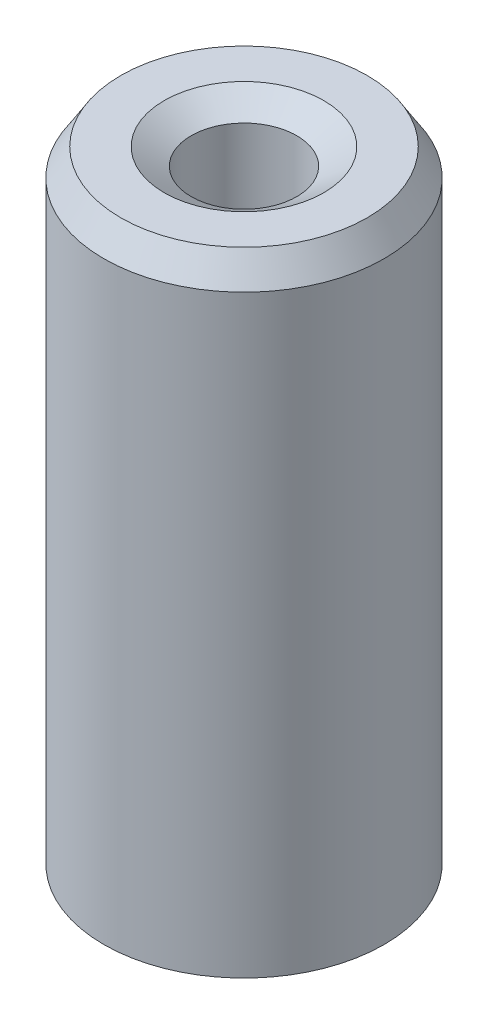
SolidWorks part; units mm, degrees
ref_plane "Front Plane" through (0, 0, 0) normal (0, 0, 1) x (1, 0, 0)
ref_plane "Top Plane" through (0, 0, 0) normal (0, 1, 0) x (1, 0, 0)
ref_plane "Right Plane" through (0, 0, 0) normal (1, 0, 0) x (0, 0, -1)
sketch "Sketch1" plane through (0, 0, 0) normal (0, 1, 0) x (1, 0, 0)
  circle A0 centre (0, 0) radius 12.5
  dimension "SLEEVE_OD" = 25
extrude "Boss-Extrude1" add sketch "Sketch1" along normal blind 56.8938
sketch "Sketch2" plane through (0, 0, 0) normal (0, 1, 0) x (1, 0, 0)
  circle A0 centre (0, 0) radius 4.7115
  dimension "BORE_D" = 9.423
extrude "Cut-Extrude1" cut sketch "Sketch2" along normal through all
chamfer "Chamfer1" distance 2.4074 angle 32.065 4 edges at (0, 56.8938, 4.7115) (0, 0, 4.7115) (0, 0, 12.5) (0, 56.8938, 12.5) first distance on face at (0, 56.8938, 4.7115) first distance on face at (0, 0, 4.7115) first distance on face at (0, 56.8938, 12.5)
